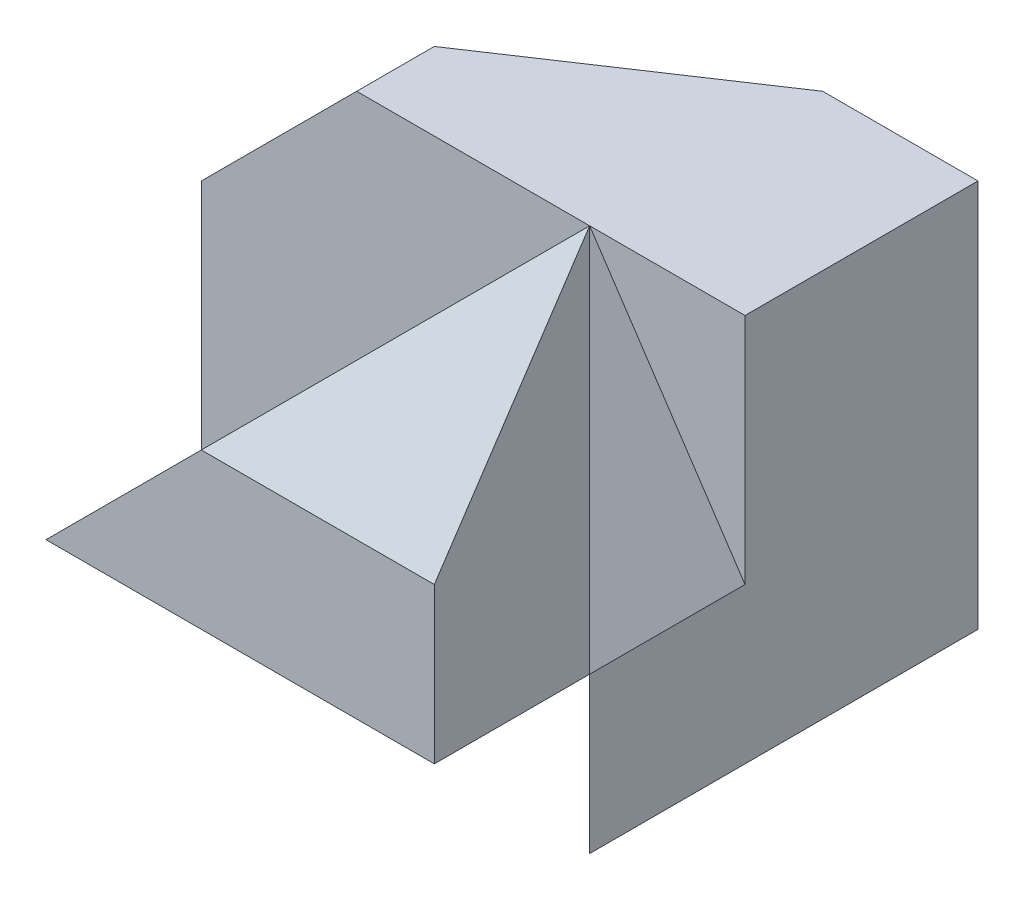
SolidWorks part; units mm, degrees
ref_plane "Front Plane" through (0, 0, 0) normal (0, 0, 1) x (1, 0, 0)
ref_plane "Top Plane" through (0, 0, 0) normal (0, 1, 0) x (1, 0, 0)
ref_plane "Right Plane" through (0, 0, 0) normal (1, 0, 0) x (0, 0, -1)
sketch "Sketch1" plane through (0, 0, 0) normal (0, 0, 1) x (1, 0, 0)
  line L0 (0, 0) -> (0, 30)
  line L1 (0, 30) -> (20, 50)
  line L2 (20, 50) -> (70, 50)
  line L3 (70, 50) -> (70, 0)
  line L4 (70, 0) -> (0, 0)
  dimension "D1" = 70
  dimension "D2" = 50
  dimension "D3" = 50
  dimension "D4" = 30
extrude "Boss-Extrude1" add sketch "Sketch1" along normal blind 50
sketch "Sketch2" plane through (0, 0, 50) normal (0, 0, 1) x (1, 0, 0)
  line L0 (0, 0) -> (50, 50)
  line L1 (70, 50) -> (20, 50) construction
  line L2 (50, 50) -> (50, 0)
  line L3 (0, 0) -> (70, 0) construction
  line L4 (50, 0) -> (0, 0)
  line L5 (50, 50) -> (20, 50)
  line L6 (20, 50) -> (0, 30)
  line L7 (0, 30) -> (0, 0)
  line M6 (70, 50) -> (20, 50)
  line M7 (20, 50) -> (0, 30)
  line M8 (0, 30) -> (0, 0)
  dimension "D1" = 50
extrude "Cut-Extrude2" cut sketch "Sketch2" against normal blind 10 contours L0 M8 M6 M7
sketch "Sketch3" plane through (0, 0, 50) normal (0, 0, 1) x (1, 0, 0)
  line L0 (20, 20) -> (50, 20)
  line L1 (0, 0) -> (50, 50) construction
  line L2 (50, 20) -> (50, 0)
  line L3 (0, 0) -> (70, 0) construction
  line L4 (50, 0) -> (0, 0)
  line L5 (20, 20) -> (0, 0)
  line L6 (0, 0) -> (50, 0)
  line M2 (50, 50) -> (0, 0)
  line M3 (0, 0) -> (70, 0)
  dimension "D1" = 20
  dimension "D2" = 20
extrude "Cut-Extrude3" cut sketch "Sketch3" against normal blind 20 contours L2 L0 M2 M3
sketch "Sketch4" plane through (0, 0, 50) normal (0, 0, 1) x (1, 0, 0)
  line L0 (50, 20) -> (50, 0) construction
  line L1 (70, 50) -> (50, 50)
  line L2 (70, 50) -> (70, 0)
  line L3 (70, 0) -> (50, 0)
  line L4 (50, 50) -> (50, 0)
  line L5 (50, 0) -> (70, 0) construction
extrude "Cut-Extrude4" cut sketch "Sketch4" against normal blind 10
sketch "Sketch5" plane through (0, 0, 40) normal (0, 0, 1) x (1, 0, 0)
  line L0 (50, 50) -> (70, 20)
  line L1 (70, 20) -> (70, 50)
  line L2 (70, 50) -> (50, 50)
  dimension "D1" = 30
extrude "Cut-Extrude5" cut sketch "Sketch5" against normal blind 10
sketch "Sketch6" plane through (0, 0, 0) normal (-1, 0, 0) x (0, 0, 1)
  line L0 (0, 0) -> (20, 30)
  line L1 (20, 30) -> (20, 50)
  line L2 (20, 50) -> (0, 50)
  line L3 (0, 50) -> (0, 0)
  dimension "D1" = 50
  dimension "D2" = 20
  dimension "D3" = 20
extrude "Cut-Extrude6" cut sketch "Sketch6" against normal blind 20
sketch "Sketch7" plane through (0, 0, 0) normal (-1, 0, 0) x (0, 0, 1)
  line L1 (20, 30) -> (30, 30)
  line L2 (20, 30) -> (20, 50)
  line L3 (20, 50) -> (30, 50)
  line L4 (30, 30) -> (30, 50)
  dimension "D1" = 10
  dimension "D2" = 20
extrude "Cut-Extrude7" cut sketch "Sketch7" against normal blind 30
sketch "Sketch8" plane through (0, 0, 0) normal (-1, 0, 0) x (0, 0, 1)
  line L0 (30, 50) -> (30, 0)
  line L1 (30, 0) -> (50, 0)
  line L2 (50, 0) -> (50, 20)
  line L3 (50, 20) -> (30, 50)
  dimension "D1" = 20
  dimension "D2" = 20
  dimension "D3" = 50
  dimension "D4" = 0
extrude "Boss-Extrude2" add sketch "Sketch8" against normal blind 30
sketch "Sketch10" plane through (0, 0, 0) normal (-1, 0, 0) x (0, 0, 1)
  line L0 (30, 50) -> (50, 20)
  line L1 (50, 20) -> (50, 50)
  line L2 (50, 50) -> (30, 50)
extrude "Cut-Extrude10" cut sketch "Sketch10" against normal blind 72
sketch "Sketch11" plane through (0, 0, 0) normal (1, 0, 0) x (0, 0, -1)
  line L0 (-30, 50) -> (-30, 0)
  line L1 (-30, 0) -> (-50, 0)
  line L2 (-50, 0) -> (0, 0) construction
  line L3 (-50, 0) -> (-50, 20)
  line L4 (-50, 20) -> (-30, 50)
extrude "Cut-Extrude13" cut sketch "Sketch11" along normal blind 10
sketch "Sketch12" plane through (0, 29.2308, 43.8462) normal (0, 0.5547, 0.8321) x (1, 0, 0)
  line L0 (30, 6.9338) -> (35, 6.9338)
  line L1 (35, 6.9338) -> (30, 0.9245)
  line L2 (30, 0.9245) -> (30, 6.9338)
extrude "Boss-Extrude3" add sketch "Sketch12" against normal blind 10
ref_plane "Plane1" through (0, 0, 50) normal (0, 0, 1) x (1, 0, 0)
sketch "Sketch14" plane through (0, 0, 50) normal (0, 0, 1) x (1, 0, 0)
  line L0 (50, 0) -> (70, 0)
  line L1 (70, 0) -> (70, 20)
  line L2 (70, 20) -> (50, 50)
  line L3 (50, 50) -> (50, 0)
  dimension "D1" = 0
  dimension "D2" = 20
  dimension "D3" = 20
  dimension "D4" = 50
extrude "Boss-Extrude4" add sketch "Sketch14" against normal blind 29
sketch "Sketch15" plane through (0, 0, 50) normal (0, 0, 1) x (1, 0, 0)
  line L0 (50, 0) -> (0, 0)
  line L1 (50, 0) -> (50, 20)
  line L2 (50, 20) -> (20, 20)
  line L3 (30, 20) -> (10, 20) construction
  line L4 (20, 20) -> (0, 0)
  dimension "D1" = 50
  dimension "D2" = 30
extrude "Boss-Extrude5" add sketch "Sketch15" against normal blind 29
sketch "Sketch16" plane through (0, 0, 50) normal (0, 0, 1) x (1, 0, 0)
  line L0 (10, 10) -> (20, 20)
  line L1 (10, 20) -> (50, 20) construction
  line L2 (20, 20) -> (10, 20)
  line L3 (10, 20) -> (10, 10)
  dimension "D1" = 10
extrude "Cut-Extrude15" cut sketch "Sketch16" against normal blind 29
sketch "Sketch17" plane through (0, 0, 50) normal (0, 0, 1) x (1, 0, 0)
  line L0 (0, 0) -> (20, 20)
  line L1 (20, 20) -> (50, 20)
  line L2 (50, 20) -> (50, 0)
  line L3 (70, 0) -> (0, 0) construction
  line L4 (50, 0) -> (0, 0)
  line L5 (50, 50) -> (50, 0)
  line L6 (50, 0) -> (70, 0)
  line L7 (70, 0) -> (70, 20)
  line L8 (70, 20) -> (50, 50)
  line M7 (0, 0) -> (70, 0)
  line M8 (70, 0) -> (70, 20)
  line M9 (70, 20) -> (50, 50)
  line M10 (50, 50) -> (50, 20)
extrude "Cut-Extrude17" cut sketch "Sketch17" against normal blind 10 contours L2 M10 M7 M8 M9
sketch "Sketch18" plane through (0, 0, 50) normal (0, 0, 1) x (1, 0, 0)
  line L0 (50, 20) -> (50, 50)
  line L1 (50, 50) -> (20, 20)
  line L2 (20, 20) -> (50, 20)
  dimension "D1" = 30
extrude "Boss-Extrude6" add sketch "Sketch18" against normal blind 35
sketch "Sketch20" plane through (0, 29.2308, 43.8462) normal (0, 0.5547, 0.8321) x (1, 0, 0)
  line L0 (20, -11.094) -> (50, 24.9615)
  line L1 (50, 24.9615) -> (10, 24.9615)
  line L2 (10, 24.9615) -> (10, -11.094)
  line L3 (10, -11.094) -> (20, -11.094)
extrude "Cut-Extrude21" cut sketch "Sketch20" against normal blind 10
sketch "Sketch26" plane through (0, 0, 50) normal (0, 0, 1) x (1, 0, 0)
  line L0 (50, 50) -> (50, 20)
  line L1 (50, 50) -> (50, 0) construction
  line L2 (50, 20) -> (20, 20)
  line L3 (50, 50) -> (20, 20) construction
  line L4 (20, 20) -> (50, 50)
  dimension "D1" = 30
extrude "Cut-Extrude23" cut sketch "Sketch26" against normal blind 10
sketch "Sketch28" plane through (0, 0, 40) normal (0, 0, 1) x (1, 0, 0)
  line L0 (50, 20) -> (50, 50)
  line L1 (50, 50) -> (24.6154, 20)
  line L2 (24.6154, 20) -> (50, 20)
extrude "Cut-Extrude24" cut sketch "Sketch28" against normal blind 10
ref_plane "Plane4" through (4.4828, -3.7931, 0) normal (-0.7634, 0.6459, 0) x (0, 0, 1)
sketch "Sketch30" plane through (4.4828, -3.7931, 0) normal (-0.7634, 0.6459, 0) x (0, 0, 1)
  line L0 (30, 70.4664) -> (40, 70.4664)
  line L1 (40, 70.4664) -> (40, 31.1678)
  line L2 (40, 31.1678) -> (30, 70.4664)
extrude "Cut-Extrude25" cut sketch "Sketch30" along normal blind 10
ref_plane "Plane5" through (0, 0, 40) normal (0, 0, 1) x (1, 0, 0)
ref_plane "Plane6" through (0, 0, 35) normal (0, 0, 1) x (1, 0, 0)
sketch "Sketch32" plane through (0, 0, 35) normal (0, 0, 1) x (1, 0, 0)
  line L0 (20, 20) -> (50, 20)
  line L1 (50, 20) -> (50, 50)
  line L2 (50, 50) -> (20, 20)
  dimension "D1" = 30
  dimension "D2" = 30
  dimension "D3" = 0
extrude "Boss-Extrude13" add sketch "Sketch32" against normal blind 19
sketch "Sketch33" plane through (0, 0, 0) normal (-0.7071, 0.7071, 0) x (0, 0, 1)
  line L0 (41.6795, 20.4396) -> (37.9815, 28.2843)
  line L1 (37.9815, 28.2843) -> (50, 28.2843)
  line L2 (50, 28.2843) -> (41.6795, 20.4396)
extrude "Boss-Extrude14" add sketch "Sketch33" against normal blind 19
sketch "Sketch34" plane through (0, 20, 0) normal (0, 1, 0) x (1, 0, 0)
  line L0 (25.547, -37.9815) -> (20, -37.9815)
  line L1 (20, -37.9815) -> (20, -50)
  line L2 (20, -50) -> (25.547, -37.9815)
extrude "Boss-Extrude15" add sketch "Sketch34" against normal blind 19
sketch "Sketch36" plane through (0, 0, 35) normal (0, 0, 1) x (1, 0, 0)
  line L0 (28.3996, 24.4722) -> (24.6154, 20)
  line L1 (24.6154, 20) -> (8.953, 20)
  line L2 (8.953, 20) -> (8.953, 24.4722)
  line L3 (8.953, 24.4722) -> (28.3996, 24.4722)
  line L4 (28.3996, 24.4722) -> (24.4722, 24.4722) construction
  dimension "D1" = 1.047
extrude "Cut-Extrude27" cut sketch "Sketch36" along normal blind 19
sketch "Sketch37" plane through (0, 0, 35) normal (0, 0, 1) x (1, 0, 0)
  line L0 (24.4722, 24.4722) -> (20, 20)
  line L1 (20, 20) -> (10, 20)
  line L2 (10, 20) -> (10, 24.4722)
  line L3 (10, 24.4722) -> (24.4722, 24.4722)
extrude "Cut-Extrude28" cut sketch "Sketch37" against normal blind 10
sketch "Sketch39" plane through (30, 0, 0) normal (-1, 0, 0) x (0, 0, 1)
  line L0 (30, 31.9722) -> (30, 50)
  line L1 (30, 50) -> (21.6795, 44.453)
  line L2 (21.6795, 44.453) -> (30, 31.9722)
extrude "Boss-Extrude16" add sketch "Sketch39" against normal blind 35
sketch "Sketch40" plane through (0, 0, 0) normal (1, 0, 0) x (0, 0, -1)
  line L0 (-30, 0) -> (-50, 0)
ref_plane "Plane7" through (20, 0, 0) normal (1, 0, 0) x (0, 0, -1)
sketch "Sketch41" plane through (20, 0, 0) normal (1, 0, 0) x (0, 0, -1)
  line L0 (-30, 0) -> (-50, 0)
  line L1 (-50, 0) -> (-50, 20)
  line L2 (-50, 20) -> (-35, 20) construction
  line L3 (-50, 20) -> (-30, 50)
  line L4 (-30, 50) -> (-30, 0)
  dimension "D1" = 20
  dimension "D2" = 20
  dimension "D3" = 0
  dimension "D4" = 50
  dimension "D5" = 10
extrude "Boss-Extrude17" add sketch "Sketch41" along normal blind 29
sketch "Sketch42" plane through (0, 0, 0) normal (-1, 0, 0) x (0, 0, 1)
  line L0 (30, 0) -> (30, 50)
  line L1 (30, 0) -> (50, 0)
  line L2 (50, 0) -> (50, 20)
  line L3 (50, 20) -> (30, 50)
  line L4 (30, 50) -> (50, 50)
  line L5 (50, 50) -> (50, 20)
  dimension "D1" = 20
  dimension "D2" = 50
extrude "Cut-Extrude29" cut sketch "Sketch42" against normal blind 108 contours L5 L4 L3
sketch "Sketch43" plane through (20, 0, 0) normal (-1, 0, 0) x (0, 0, 1)
  line L0 (30, 50) -> (30, 20)
  line L1 (30, 20) -> (50, 20)
  line L2 (50, 20) -> (30, 50)
extrude "Boss-Extrude18" add sketch "Sketch43" against normal blind 30
sketch "Sketch44" plane through (10, 0, 0) normal (-1, 0, 0) x (0, 0, 1)
  line L0 (30, 24.4722) -> (30, 31.9722)
  line L1 (30, 31.9722) -> (35, 24.4722) construction
  line L2 (30, 31.9722) -> (35, 24.4722)
  line L3 (35, 24.4722) -> (30, 24.4722)
extrude "Cut-Extrude30" cut sketch "Sketch44" against normal blind 10
sketch "Sketch45" plane through (0, 0, 50) normal (0, 0, 1) x (1, 0, 0)
  line L0 (20, 20) -> (50, 50)
  line L1 (50, 20) -> (50, 50)
  line L4 (20, 20) -> (20, 50)
  line L5 (50, 50) -> (20, 50)
  dimension "D1" = 30
extrude "Cut-Extrude31" cut sketch "Sketch45" against normal blind 20 contours L0 L5 L4
sketch "Sketch48" plane through (0, 0, 40) normal (0, 0, 1) x (1, 0, 0)
  line L0 (50, 35) -> (50, 50)
  line L1 (50, 50) -> (70, 20)
  line L2 (70, 20) -> (70, 0)
  line L3 (70, 0) -> (50, 0)
  line L4 (50, 0) -> (50, 50)
  line M1 (70, 20) -> (60, 35)
  line M2 (60, 35) -> (50, 35)
  line M3 (50, 35) -> (50, 0)
  line M4 (50, 0) -> (70, 0)
  line M5 (70, 0) -> (70, 20)
  dimension "D1" = 30
extrude "Cut-Extrude34" cut sketch "Sketch48" against normal blind 10 contours M5 M1 M2 M3 M4 | L1 L0 M2
sketch "Sketch49" plane through (0, 0, 30) normal (0, 0, 1) x (1, 0, 0)
  line L0 (50, 50) -> (70, 20)
  line L1 (70, 0) -> (70, 50) construction
  line L2 (70, 20) -> (70, 50)
  line L3 (70, 50) -> (50, 50)
  dimension "D1" = 30
extrude "Cut-Extrude35" cut sketch "Sketch49" against normal blind 10
ref_plane "Plane10" through (0, 0, 20) normal (0, 0, 1) x (1, 0, 0)
sketch "Sketch51" plane through (0, 0, 20) normal (0, 0, 1) x (1, 0, 0)
  line L0 (0, 30) -> (20, 50)
  line L1 (20, 50) -> (20, 30)
  line L2 (20, 30) -> (0, 30)
  line L3 (20, 50) -> (30, 50)
  line L4 (30, 50) -> (30, 30)
  line L5 (30, 30) -> (20, 30)
extrude "Boss-Extrude20" add sketch "Sketch51" along normal blind 10 contours L5 L4 L3 L1 | L2 L1 L0
sketch "Sketch52" plane through (0, 0, 30) normal (0, 0, 1) x (1, 0, 0)
  line L0 (10, 10) -> (24.4722, 24.4722)
  line L1 (24.4722, 24.4722) -> (10, 24.4722)
  line L2 (10, 24.4722) -> (10, 10)
extrude "Boss-Extrude21" add sketch "Sketch52" against normal blind 10
sketch "Sketch53" plane through (0, 0, 0) normal (0, 1, 0) x (1, 0, 0)
  line L0 (70, -30) -> (70, -50)
  line L1 (70, -50) -> (50, -30)
  line L2 (50, -30) -> (70, -30)
  dimension "D1" = 20
extrude "Boss-Extrude23" add sketch "Sketch53" along normal blind 50
sketch "Sketch54" plane through (0, 0, 30) normal (0, 0, -1) x (-1, 0, 0)
  line L0 (-70, 20) -> (-50, 50)
  line L1 (-50, 50) -> (-70, 50)
  line L2 (-70, 50) -> (-70, 20)
extrude "Cut-Extrude36" cut sketch "Sketch54" against normal blind 50
ref_plane "Plane11" through (0, 20, 0) normal (0, 1, 0) x (1, 0, 0)
sketch "Sketch55" plane through (0, 20, 0) normal (0, 1, 0) x (1, 0, 0)
  line L1 (70, -20) -> (50, -20)
  line L2 (70, -20) -> (70, -29.999)
  line L3 (70, -29.999) -> (50, -29.999)
  line L4 (50, -20) -> (50, -29.999)
  dimension "D1" = 20
  dimension "D2" = 9.999
extrude "Cut-Extrude41" cut sketch "Sketch55" along normal blind 50
sketch "Sketch57" plane through (0, 20, 0) normal (0, 1, 0) x (1, 0, 0)
  line L1 (50, -29.999) -> (70, -29.999)
  line L2 (50, -29.999) -> (50, -20)
  line L3 (50, -20) -> (70, -20)
  line L4 (70, -29.999) -> (70, -20)
extrude "Boss-Extrude24" add sketch "Sketch57" along normal blind 30
sketch "Sketch58" plane through (0, 50, 0) normal (0, 1, 0) x (1, 0, 0)
  line L0 (50, 0) -> (70, 0)
  line L1 (70, 0) -> (20, 0) construction
  line L2 (70, 0) -> (70, -29.999)
  line L3 (70, -29.999) -> (20, -30)
  line L4 (20, -30) -> (20, -20)
  line L5 (20, -20) -> (50, 0)
  line L6 (20, -20) -> (20, 0)
  line L7 (20, 0) -> (50, 0)
  dimension "D1" = 20
extrude "Cut-Extrude45" cut sketch "Sketch58" against normal blind 10
sketch "Sketch59" plane through (0, 40, 0) normal (0, 1, 0) x (1, 0, 0)
  line L0 (20, 0) -> (20, -20)
  line L1 (20, -20) -> (50, 0)
  line L2 (50, 0) -> (20, 0)
extrude "Cut-Extrude46" cut sketch "Sketch59" against normal blind 40
sketch "Sketch60" plane through (0, 0, 0) normal (0, -1, 0) x (1, 0, 0)
  line L0 (20, 0) -> (50, 0)
  line L1 (50, 0) -> (20, 20)
  line L2 (20, 20) -> (20, 0)
extrude "Boss-Extrude25" add sketch "Sketch60" against normal blind 0.0001
ref_plane "Plane12" through (0, 0, 0) normal (0, -0.5547, 0.832) x (1, 0, 0)
sketch "Sketch61" plane through (0, 0, 0) normal (0, -0.5547, 0.832) x (1, 0, 0)
  line L0 (50, 0.0001) -> (20, 36.0555)
  line L1 (20, 36.0555) -> (20, 0.0001)
  line L2 (20, 0.0001) -> (50, 0.0001)
extrude "Boss-Extrude28" add sketch "Sketch61" along normal blind 10
ref_plane "Plane13" through (0, 0, 0) normal (0, 0.5547, -0.8321) x (-1, 0, 0)
sketch "Sketch62" plane through (0, 0, 0) normal (0, 0.5547, -0.8321) x (-1, 0, 0)
  line L0 (-20, 36.0555) -> (0, 36.0555)
  line L1 (0, 36.0555) -> (-4.723, 0)
  line L2 (0, 0) -> (-20, 0) construction
  line L3 (-4.723, 0) -> (-50, 0.0001)
  dimension "D1" = 45.277
extrude "Extrude-Thin1" add sketch "Sketch62" against normal blind 10 thin
ref_plane "Plane14" through (0, 0, 0) normal (0, 0.5547, -0.832) x (-1, 0, 0)
sketch "Sketch63" plane through (0, 0, 0) normal (0, 0.5547, -0.832) x (-1, 0, 0)
  line L0 (-20, 36.0555) -> (0, 0)
  line L1 (0, 0) -> (-50, 0.0001)
  line L2 (-50, 0.0001) -> (-20, 36.0555)
extrude "Boss-Extrude30" add sketch "Sketch63" against normal blind 10
sketch "Sketch64" plane through (0, 0, 0) normal (0, -1, 0) x (-1, 0, 0)
  line L0 (-50, -12.0187) -> (-50, -0.0002)
  line L1 (-50, -0.0002) -> (0, 0)
  line L2 (0, 0) -> (-3.698, -12.0185)
  line L3 (-3.698, -12.0185) -> (-50, -12.0187)
  line L4 (-3.8497, -12.0185) -> (-50, -12.0187) construction
extrude "Cut-Extrude48" cut sketch "Sketch64" along normal blind 10
sketch "Sketch67" plane through (0, 0, 0) normal (-0.8745, 0.4036, 0.2691) x (0.2443, -0.1128, 0.9631)
  line L0 (8.6391, -5.0365) -> (0, 0)
  line L1 (0, 0) -> (12.4787, 1.5497)
  line L2 (12.4787, 1.5497) -> (8.6391, -5.0365)
extrude "Cut-Extrude50" cut sketch "Sketch67" against normal blind 10
sketch "Sketch68" plane through (0, 0, 0) normal (0, -1, 0) x (1, 0, 0)
  line L0 (4.723, 0) -> (20, 0.0001) construction
  line L1 (12.3754, 2.2934) -> (38.0994, 2.2934)
  line L2 (12.3754, 2.2934) -> (12.3754, 27.7073)
  line L3 (12.3754, 27.7073) -> (38.0994, 27.7073)
  line L4 (38.0994, 2.2934) -> (38.0994, 27.7073)
  line L5 (0, 30) -> (0, 0) construction
  dimension "D1" = 25.7239
  dimension "D2" = 25.4139
  dimension "D3" = 2.2934
  dimension "D4" = 12.3754
extrude "Boss-Extrude39" add sketch "Sketch68" against normal blind 1
ref_plane "Plane15" through (0, 0, 0) normal (0, -0.5547, 0.832) x (1, 0, 0)
